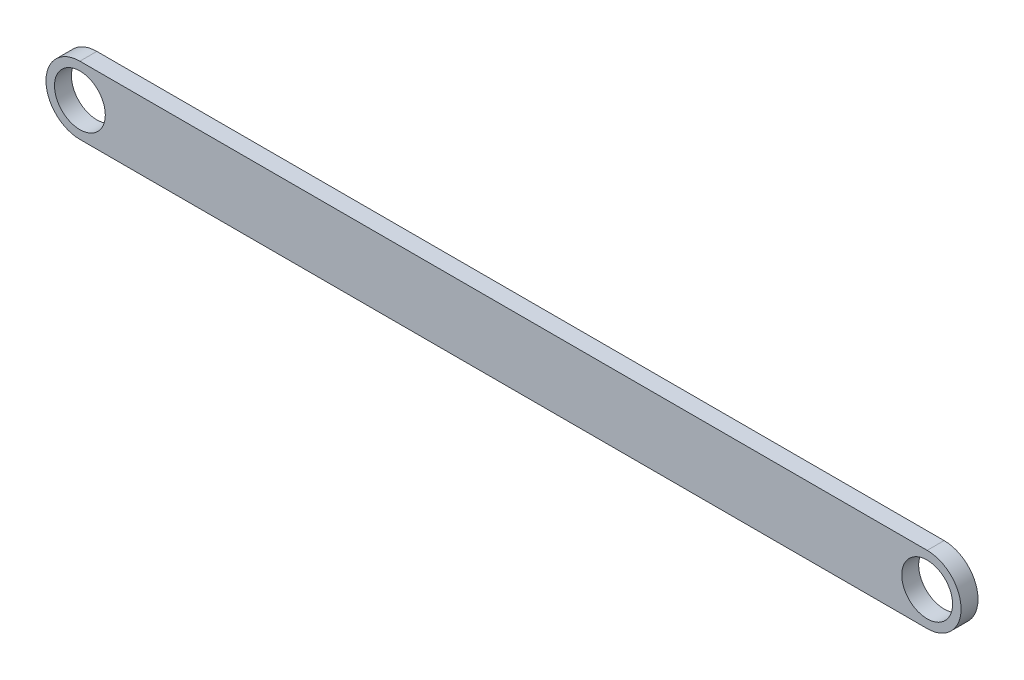
SolidWorks part; units mm, degrees
ref_plane "Спереди" through (0, 0, 0) normal (0, 0, 1) x (1, 0, 0)
ref_plane "Сверху" through (0, 0, 0) normal (0, 1, 0) x (1, 0, 0)
ref_plane "Справа" through (0, 0, 0) normal (1, 0, 0) x (0, 0, -1)
other "Configuration Table"
sketch "Эскиз1" plane through (0, 0, 0) normal (0, 0, 1) x (1, 0, 0)
  line L0 (0, 0) -> (500, 0) construction
  line L1 (0, 20) -> (500, 20)
  line L2 (0, -20) -> (500, -20)
  arc A0 (0, 20) -> (0, -20) centre (0, 0) ccw
  arc A1 (500, -20) -> (500, 20) centre (500, 0) ccw
  circle A2 centre (0, 0) radius 15
  circle A3 centre (500, 0) radius 15
  point P3 (250, 0)
  dimension "D3" = 30
  dimension "D4" = 30
  dimension "D1" = 500
  dimension "D2" = 40
extrude "Бобышка-Вытянуть3" add sketch "Эскиз1" along normal blind 10
